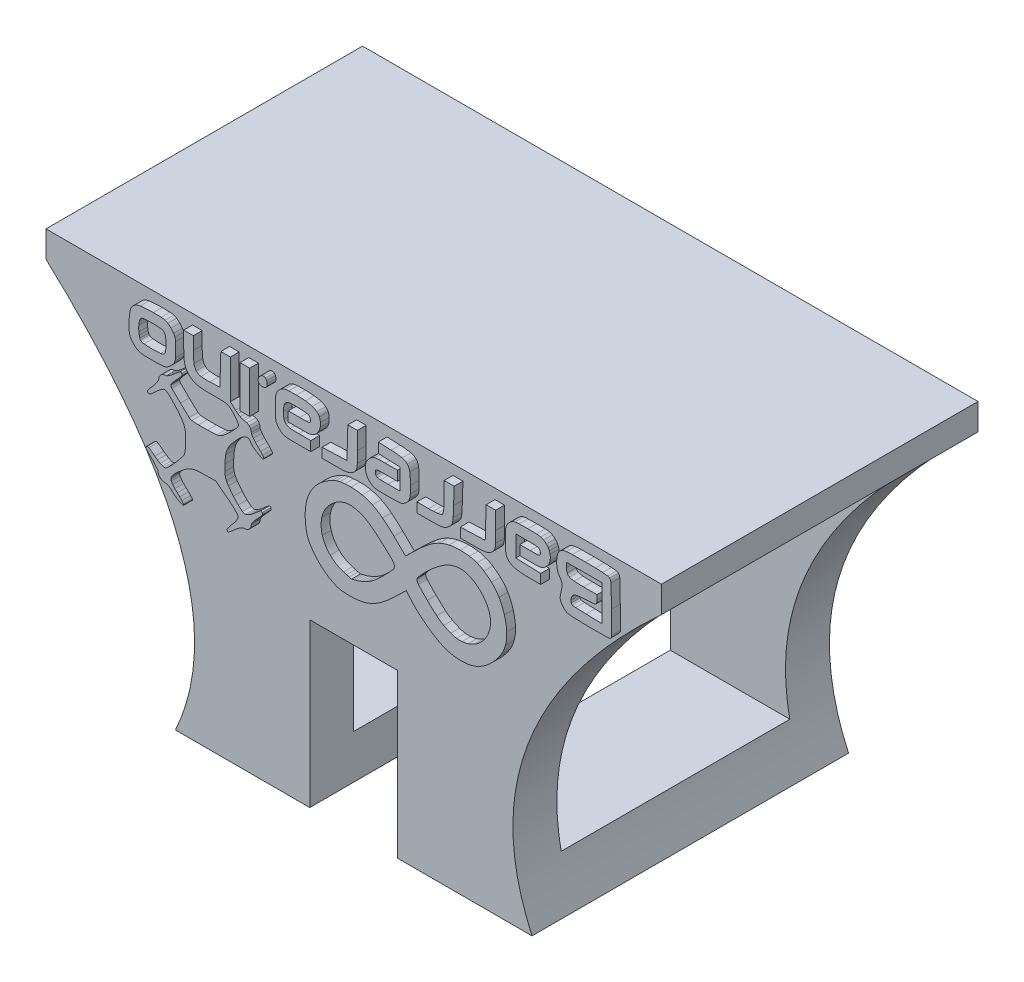
SolidWorks part; units mm, degrees
ref_plane "Alzado" through (0, 0, 0) normal (0, 0, 1) x (1, 0, 0)
ref_plane "Planta" through (0, 0, 0) normal (0, 1, 0) x (1, 0, 0)
ref_plane "Vista lateral" through (0, 0, 0) normal (1, 0, 0) x (0, 0, -1)
sketch "Croquis1" plane through (0, 0, 0) normal (0, 0, 1) x (1, 0, 0)
  line L1 (-15, 9.25) -> (15, 9.25)
  line L2 (-15, 9.25) -> (-15, -9.25)
  line L3 (-15, -9.25) -> (15, -9.25)
  line L4 (15, 9.25) -> (15, -9.25)
  line L5 (-15, 9.25) -> (15, -9.25) construction
  line L6 (-15, -9.25) -> (15, 9.25) construction
  point P0 (0, 0)
  dimension "D1" = 30
  dimension "D2" = 18.5
extrude "Saliente-Extruir1" add sketch "Croquis1" along normal blind 13
shell "Vaciado2" thickness 2.5 removed face at (0, 9.25, 6.5) outward yes
sketch "Croquis2" plane through (0, 0, -2.5) normal (0, 0, -1) x (-1, 0, 0)
  line L0 (2.5, -11.75) -> (10.1401, -11.75)
  line L1 (17.5, 9.25) -> (17.5, -11.75) construction
  line L2 (17.5, 9.25) -> (17.5, 7.75)
  line L4 (2.5, -11.75) -> (2.5, -2.5)
  line L5 (2.5, -2.5) -> (-2.5, -2.5)
  line L6 (0, -2.5) -> (0, -0.2637) construction
  line L7 (-2.5, -11.75) -> (-2.5, -2.5)
  line L8 (-17.5, 9.25) -> (-17.5, 7.75)
  line L9 (-2.5, -11.75) -> (-10.1401, -11.75)
  line L10 (17.5, 9.25) -> (-17.5, 9.25)
  line L11 (17.5, -11.75) -> (-17.5, -11.75) construction
  line L12 (17.5, 7.75) -> (17.5, -11.75)
  line L13 (17.5, -11.75) -> (10.1401, -11.75)
  line L14 (-17.5, 7.75) -> (-17.5, -11.75)
  line L15 (-17.5, -11.75) -> (-10.1401, -11.75)
  line L16 (-17.5, -11.75) -> (-17.5, 9.25) construction
  spline S0 degree 2 poles (17.5, 7.75) (6.0206, -2.776) (10.1401, -11.75) knots 0 0 0 0.858942 0.858942 0.858942
  spline S1 degree 2 poles (-17.5, 7.75) (-6.0206, -2.776) (-10.1401, -11.75) knots 0 0 0 0.858942 0.858942 0.858942
  line M13 (-17.5, -11.75) -> (17.5, -11.75)
  line M14 (17.5, -11.75) -> (17.5, 9.25)
  dimension "D1" = 1.5
  dimension "D2" = 2.5
extrude "Cortar-Extruir1" cut sketch "Croquis2" against normal blind 33 contours S0 M14 M13 | S1 L14 M13 | L7 L4 L5 M13 region at (0, -7.125, -2.5) region at (-13.9189, -3.9974, -2.5) region at (13.9189, -3.9974, -2.5)
sketch "Croquis3" plane through (0, 9.25, 0) normal (0, 1, 0) x (1, 0, 0)
  line L0 (-17.5, 2.5) -> (-17.5, -15.5)
  line L1 (-17.5, -15.5) -> (17.5, -15.5)
  line L2 (17.5, -15.5) -> (17.5, 2.5)
  line L3 (17.5, 2.5) -> (-17.5, 2.5)
extrude "Saliente-Extruir2" add sketch "Croquis3" against normal blind 1.5
sketch "Croquis4" plane through (-17.5, 0, 0) normal (-1, 0, 0) x (0, 0, 1)
  line L0 (13, -9.25) -> (13, 7.75)
  line L1 (15.5, 7.75) -> (-2.5, 7.75) construction
  line L2 (13, 7.75) -> (0, 7.75)
  line L3 (0, 7.75) -> (0, -9.25)
  line L4 (0, -9.25) -> (13, -9.25)
extrude "Cortar-Extruir2" cut sketch "Croquis4" against normal blind 36.5
sketch "Croquis5" plane through (0, 0, 15.5) normal (0, 0, 1) x (1, 0, 0)
  line L0 (-6.7264, 1.6869) -> (-7.3476, 2.1605)
  line L1 (-7.3476, 2.1605) -> (-8.0126, 2.1501)
  line L2 (-9.1685, 7.909) -> (-9.1685, 8.6803)
  line L3 (-9.1685, 8.6803) -> (-8.8942, 8.6803)
  line L4 (-8.8942, 8.6803) -> (-8.6199, 8.6803)
  line L5 (-8.6199, 8.6803) -> (-8.6199, 7.9488)
  line L6 (-7.6784, 6.8701) -> (-7.1111, 6.8972)
  line L7 (-7.1111, 6.8972) -> (-7.0849, 7.7888)
  line L8 (-7.0849, 7.7888) -> (-7.0588, 8.6803)
  line L9 (-7.0588, 8.6803) -> (-6.7878, 8.6803)
  line L10 (-6.7878, 8.6803) -> (-6.5168, 8.6803)
  line L11 (-6.5168, 8.6803) -> (-6.5168, 7.5817)
  line L12 (-6.5168, 7.5817) -> (-6.5168, 6.4832)
  line L13 (-6.5168, 6.4832) -> (-6.2196, 6.2128)
  line L14 (3.8426, 1.768) -> (3.4836, 2.1759)
  line L15 (3.4836, 2.1759) -> (2.8013, 1.5191)
  line L16 (2.7863, 4.5105) -> (3.4488, 3.8611)
  line L17 (3.4488, 3.8611) -> (4.1178, 4.5105)
  line L18 (10.5867, 7.1258) -> (9.9424, 7.1258)
  line L19 (9.9424, 7.1258) -> (9.9424, 7.4002)
  line L20 (9.9424, 7.4002) -> (9.9424, 7.6745)
  line L21 (9.9424, 7.6745) -> (10.5432, 7.6745)
  line L22 (10.3996, 8.086) -> (9.7138, 8.086)
  line L23 (9.7138, 8.086) -> (9.7138, 7.4916)
  line L24 (9.7138, 7.4916) -> (9.7138, 6.8972)
  line L25 (9.7138, 6.8972) -> (10.4225, 6.8705)
  line L26 (10.4225, 6.8705) -> (11.1312, 6.8438)
  line L27 (11.1312, 6.8438) -> (11.1312, 6.5733)
  line L28 (11.1312, 6.5733) -> (11.1312, 6.3029)
  line L29 (11.1312, 6.3029) -> (10.4408, 6.3029)
  line L30 (6.5592, 6.5733) -> (6.5592, 6.8438)
  line L31 (6.5592, 6.8438) -> (7.2678, 6.8705)
  line L32 (7.2678, 6.8705) -> (7.9765, 6.8972)
  line L33 (7.9765, 6.8972) -> (8.0027, 7.7888)
  line L34 (8.0027, 7.7888) -> (8.0288, 8.6803)
  line L35 (8.0288, 8.6803) -> (8.2998, 8.6803)
  line L36 (8.2998, 8.6803) -> (8.5708, 8.6803)
  line L37 (8.5708, 8.6803) -> (8.5708, 7.6811)
  line L38 (7.3241, 6.3029) -> (6.5592, 6.3029)
  line L39 (6.5592, 6.3029) -> (6.5592, 6.5733)
  line L40 (4.0903, 6.5772) -> (4.0903, 6.8515)
  line L41 (4.0903, 6.8515) -> (4.7578, 6.8515)
  line L42 (5.6448, 7.8756) -> (5.6448, 8.6803)
  line L43 (5.6448, 8.6803) -> (5.9274, 8.6803)
  line L44 (5.9274, 8.6803) -> (6.2101, 8.6803)
  line L45 (6.2101, 8.6803) -> (6.1789, 7.7121)
  line L46 (4.8624, 6.3029) -> (4.0903, 6.3029)
  line L47 (4.0903, 6.3029) -> (4.0903, 6.5772)
  line L48 (2.3031, 7.8574) -> (2.993, 7.8574)
  line L49 (2.993, 7.8574) -> (2.993, 7.583)
  line L50 (2.993, 7.583) -> (2.993, 7.3087)
  line L51 (2.993, 7.3087) -> (2.3466, 7.3087)
  line L52 (2.4444, 6.8972) -> (3.1302, 6.8972)
  line L53 (3.1302, 6.8972) -> (3.1302, 7.4916)
  line L54 (3.1302, 7.4916) -> (3.1302, 8.086)
  line L55 (3.1302, 8.086) -> (2.5129, 8.113)
  line L56 (2.5129, 8.113) -> (1.8957, 8.14)
  line L57 (1.8957, 8.14) -> (1.8957, 8.4199)
  line L58 (1.8957, 8.4199) -> (1.8957, 8.6997)
  line L59 (1.8957, 8.6997) -> (2.6362, 8.6661)
  line L60 (-1.3047, 6.5733) -> (-1.3047, 6.8438)
  line L61 (-1.3047, 6.8438) -> (-0.596, 6.8705)
  line L62 (-0.596, 6.8705) -> (0.1126, 6.8972)
  line L63 (0.1126, 6.8972) -> (0.1388, 7.7888)
  line L64 (0.1388, 7.7888) -> (0.165, 8.6803)
  line L65 (0.165, 8.6803) -> (0.436, 8.6803)
  line L66 (0.436, 8.6803) -> (0.707, 8.6803)
  line L67 (0.707, 8.6803) -> (0.707, 7.6811)
  line L68 (-0.5398, 6.3029) -> (-1.3047, 6.3029)
  line L69 (-1.3047, 6.3029) -> (-1.3047, 6.5733)
  line L70 (-2.535, 7.1258) -> (-3.2249, 7.1258)
  line L71 (-3.2249, 7.1258) -> (-3.2249, 7.4002)
  line L72 (-3.2249, 7.4002) -> (-3.2249, 7.6745)
  line L73 (-3.2249, 7.6745) -> (-2.5785, 7.6745)
  line L74 (-2.6273, 6.8515) -> (-1.9448, 6.8515)
  line L75 (-1.9448, 6.8515) -> (-1.9448, 6.5772)
  line L76 (-1.9448, 6.5772) -> (-1.9448, 6.3029)
  line L77 (-1.9448, 6.3029) -> (-2.7261, 6.3029)
  line L78 (-5.9681, 7.4916) -> (-5.9681, 8.6803)
  line L79 (-5.9681, 8.6803) -> (-5.6938, 8.6803)
  line L80 (-5.6938, 8.6803) -> (-5.4195, 8.6803)
  line L81 (-5.4195, 8.6803) -> (-5.4195, 7.4916)
  line L82 (-5.4195, 7.4916) -> (-5.4195, 6.3029)
  line L83 (-5.4195, 6.3029) -> (-5.6938, 6.3029)
  line L84 (-5.6938, 6.3029) -> (-5.9681, 6.3029)
  line L85 (-5.9681, 6.3029) -> (-5.9681, 7.4916)
  line L86 (0.2431, 1.2245) -> (0.3739, 1.189)
  line L87 (14.6059, 7.1225) -> (14.6059, 8.1317)
  line L88 (14.6059, 8.1317) -> (13.6, 8.1317)
  line L89 (13.6, 8.1317) -> (12.5942, 8.1317)
  line L90 (12.5942, 8.1317) -> (12.5942, 7.8756)
  line L91 (13.5726, 7.4002) -> (14.3316, 7.4002)
  line L92 (14.3316, 7.4002) -> (14.3316, 7.1362)
  line L93 (13.7143, 6.1395) -> (14.6059, 6.1134)
  line L94 (14.6059, 6.1134) -> (14.6059, 7.1225)
  arc A0 (-6.6839, 0.1379) -> (-6.6996, 0.0847) centre (-6.6016, 0.0847) ccw
  arc A1 (-6.6034, 0.2555) -> (-6.6839, 0.1379) centre (-4.3185, -1.3938) ccw
  arc A2 (-6.4976, 0.3928) -> (-6.6034, 0.2555) centre (-4.3742, -1.3536) ccw
  arc A3 (-6.3722, 0.5383) -> (-6.4976, 0.3928) centre (-3.3013, -2.2361) ccw
  arc A4 (-6.3722, 0.5383) -> (-6.2491, 0.6885) centre (-7.8715, 1.8929) ccw
  arc A5 (-6.2491, 0.6885) -> (-6.1498, 0.8402) centre (-7.4802, 1.6024) ccw
  arc A6 (-6.1498, 0.8402) -> (-6.0837, 0.9739) centre (-7.2143, 1.45) ccw
  arc A7 (-6.0837, 0.9739) -> (-6.075, 1.057) centre (-6.2161, 1.0297) ccw
  arc A8 (-6.075, 1.057) -> (-6.1181, 1.1421) centre (-6.2459, 1.0239) ccw
  arc A9 (-6.1181, 1.1421) -> (-6.2788, 1.3065) centre (-9.1303, -1.6424) ccw
  arc A10 (-6.2788, 1.3065) -> (-6.4863, 1.4941) centre (-9.1839, -1.6979) ccw
  arc A11 (-6.4863, 1.4941) -> (-6.7264, 1.6869) centre (-10.4438, -3.1887) ccw
  arc A12 (-8.0126, 2.1501) -> (-8.4856, 2.1181) centre (-7.9414, -2.4118) ccw
  arc A13 (-8.4856, 2.1181) -> (-8.8052, 2.0314) centre (-8.3493, 0.9838) ccw
  arc A14 (-8.8052, 2.0314) -> (-9.1088, 1.8499) centre (-8.2532, 0.7631) ccw
  arc A15 (-9.1088, 1.8499) -> (-9.5418, 1.4846) centre (-3.9405, -4.7153) ccw
  arc A16 (-9.5418, 1.4846) -> (-9.6789, 1.348) centre (-8.2072, 0.0074) ccw
  arc A17 (-9.6789, 1.348) -> (-9.7948, 1.2054) centre (-8.4807, 0.2565) ccw
  arc A18 (-9.7948, 1.2054) -> (-9.8774, 1.0757) centre (-8.7272, 0.4345) ccw
  arc A19 (-9.8774, 1.0757) -> (-9.9, 0.9885) centre (-9.7209, 0.9885) ccw
  arc A20 (-9.9, 0.9885) -> (-9.877, 0.9009) centre (-9.722, 0.9885) ccw
  arc A21 (-9.877, 0.9009) -> (-9.7926, 0.7696) centre (-8.6924, 1.5697) ccw
  arc A22 (-9.7926, 0.7696) -> (-9.6743, 0.6247) centre (-8.4411, 1.7525) ccw
  arc A23 (-9.6743, 0.6247) -> (-9.5343, 0.4856) centre (-8.1452, 2.0231) ccw
  arc A24 (-9.3942, 0.3529) -> (-9.5343, 0.4856) centre (-12.3125, -2.5897) ccw
  arc A25 (-9.276, 0.2278) -> (-9.3942, 0.3529) centre (-11.2475, -1.5158) ccw
  arc A26 (-9.1853, 0.1199) -> (-9.276, 0.2278) centre (-11.3717, -1.6256) ccw
  arc A27 (-9.1685, 0.072) -> (-9.1853, 0.1199) centre (-9.2453, 0.072) ccw
  arc A28 (-9.224, 0.0333) -> (-9.1685, 0.072) centre (-9.2098, 0.072) ccw
  arc A29 (-9.4288, 0.1263) -> (-9.224, 0.0333) centre (-8.6911, 1.479) ccw
  arc A30 (-9.6633, 0.276) -> (-9.4288, 0.1263) centre (-8.4622, 1.8987) ccw
  arc A31 (-9.8458, 0.4414) -> (-9.6633, 0.276) centre (-8.9223, 1.2772) ccw
  arc A32 (-9.8458, 0.4414) -> (-9.9269, 0.5149) centre (-10.2599, 0.0667) ccw
  arc A33 (-9.9269, 0.5149) -> (-10.0263, 0.5771) centre (-10.3649, -0.0747) ccw
  arc A34 (-10.0263, 0.5771) -> (-10.1282, 0.6197) centre (-10.3337, -0.0146) ccw
  arc A35 (-10.1282, 0.6197) -> (-10.216, 0.6336) centre (-10.216, 0.3489) ccw
  arc A36 (-10.3737, 0.6604) -> (-10.216, 0.6336) centre (-10.216, 1.1106) ccw
  arc A37 (-10.5087, 0.7378) -> (-10.3737, 0.6604) centre (-10.2324, 1.0636) ccw
  arc A38 (-10.5994, 0.8524) -> (-10.5087, 0.7378) centre (-10.2682, 1.0214) ccw
  arc A39 (-10.6316, 0.986) -> (-10.5994, 0.8524) centre (-10.3376, 0.986) ccw
  arc A40 (-10.6316, 0.986) -> (-10.6532, 1.0581) centre (-10.7625, 0.986) ccw
  arc A41 (-10.6532, 1.0581) -> (-10.7457, 1.1867) centre (-12.291, -0.022) ccw
  arc A42 (-10.7457, 1.1867) -> (-10.8714, 1.3337) centre (-12.4962, -0.1825) ccw
  arc A43 (-10.8714, 1.3337) -> (-11.0202, 1.4828) centre (-13.1565, -0.7988) ccw
  arc A44 (-11.3012, 1.7729) -> (-11.0202, 1.4828) centre (-8.1957, 4.4992) ccw
  arc A45 (-11.2909, 1.8907) -> (-11.3012, 1.7729) centre (-11.2397, 1.8269) ccw
  arc A46 (-11.1513, 1.897) -> (-11.2909, 1.8907) centre (-11.2168, 1.7986) ccw
  arc A47 (-10.813, 1.6493) -> (-11.1513, 1.897) centre (-13.7376, -1.9899) ccw
  arc A48 (-10.813, 1.6493) -> (-10.6646, 1.5405) centre (-9.5138, 3.266) ccw
  arc A49 (-10.6646, 1.5405) -> (-10.5112, 1.4486) centre (-9.6371, 3.0811) ccw
  arc A50 (-10.5112, 1.4486) -> (-10.3733, 1.3833) centre (-9.778, 2.818) ccw
  arc A51 (-10.3733, 1.3833) -> (-10.2823, 1.3651) centre (-10.2823, 1.6028) ccw
  arc A52 (-10.2823, 1.3651) -> (-10.1369, 1.4187) centre (-10.2823, 1.589) ccw
  arc A53 (-10.1369, 1.4187) -> (-9.8831, 1.655) centre (-12.7471, 4.4772) ccw
  arc A54 (-9.8831, 1.655) -> (-9.5662, 2.004) centre (-13.9973, 5.7092) ccw
  arc A55 (-9.5662, 2.004) -> (-9.1803, 2.4834) centre (-22.2046, 12.5721) ccw
  arc A56 (-9.1803, 2.4834) -> (-9.1289, 2.5874) centre (-9.411, 2.6621) ccw
  arc A57 (-9.1289, 2.5874) -> (-9.0907, 2.7703) centre (-10.837, 3.0392) ccw
  arc A58 (-9.0907, 2.7703) -> (-9.0659, 3.0039) centre (-11.5655, 3.1514) ccw
  arc A59 (-9.0659, 3.0039) -> (-9.0578, 3.2787) centre (-13.7232, 3.2787) ccw
  arc A60 (-9.0578, 3.2787) -> (-9.0672, 3.6176) centre (-15.1794, 3.2787) ccw
  arc A61 (-9.0672, 3.6176) -> (-9.0989, 3.8493) centre (-10.5155, 3.5373) ccw
  arc A62 (-9.0989, 3.8493) -> (-9.161, 4.0347) centre (-9.9991, 3.651) ccw
  arc A63 (-9.161, 4.0347) -> (-9.2647, 4.2178) centre (-10.2798, 3.5225) ccw
  arc A64 (-9.2647, 4.2178) -> (-9.5264, 4.5628) centre (-12.9564, 1.6889) ccw
  arc A65 (-9.5264, 4.5628) -> (-9.8258, 4.8889) centre (-13.2728, 1.4237) ccw
  arc A66 (-9.8258, 4.8889) -> (-10.1083, 5.1502) centre (-13.5572, 1.1378) ccw
  arc A67 (-10.1083, 5.1502) -> (-10.2576, 5.2056) centre (-10.2576, 4.9765) ccw
  arc A68 (-10.2576, 5.2056) -> (-10.331, 5.1862) centre (-10.2576, 5.0573) ccw
  arc A69 (-10.331, 5.1862) -> (-10.4542, 5.1085) centre (-9.5215, 3.7649) ccw
  arc A70 (-10.4542, 5.1085) -> (-10.594, 5.0017) centre (-9.3616, 3.5346) ccw
  arc A71 (-10.594, 5.0017) -> (-10.7336, 4.8752) centre (-8.9737, 3.0728) ccw
  arc A72 (-11.0497, 4.5919) -> (-10.7336, 4.8752) centre (-14.1962, 8.4211) ccw
  arc A73 (-11.1886, 4.5835) -> (-11.0497, 4.5919) centre (-11.1249, 4.6834) ccw
  arc A74 (-11.2094, 4.6969) -> (-11.1886, 4.5835) centre (-11.1463, 4.6499) ccw
  arc A75 (-10.9498, 5.0127) -> (-11.2094, 4.6969) centre (-7.6966, 2.0737) ccw
  arc A76 (-10.9498, 5.0127) -> (-10.8135, 5.1759) centre (-12.9674, 6.8355) ccw
  arc A77 (-10.8135, 5.1759) -> (-10.6963, 5.3428) centre (-12.6411, 6.5841) ccw
  arc A78 (-10.6963, 5.3428) -> (-10.6101, 5.492) centre (-12.3463, 6.3959) ccw
  arc A79 (-10.6101, 5.492) -> (-10.583, 5.5874) centre (-10.8278, 5.6054) ccw
  arc A80 (-10.5453, 5.7213) -> (-10.583, 5.5874) centre (-10.2353, 5.5618) ccw
  arc A81 (-10.4576, 5.8335) -> (-10.5453, 5.7213) centre (-10.2064, 5.5469) ccw
  arc A82 (-10.3319, 5.9085) -> (-10.4576, 5.8335) centre (-10.1905, 5.5287) ccw
  arc A83 (-10.1854, 5.9357) -> (-10.3319, 5.9085) centre (-10.1806, 5.5022) ccw
  arc A84 (-10.1854, 5.9357) -> (-10.1157, 5.9548) centre (-10.187, 6.0783) ccw
  arc A85 (-10.1157, 5.9548) -> (-9.9872, 6.0353) centre (-11.1796, 7.7956) ccw
  arc A86 (-9.9872, 6.0353) -> (-9.8393, 6.1442) centre (-11.311, 7.9896) ccw
  arc A87 (-9.8393, 6.1442) -> (-9.6877, 6.2728) centre (-11.8554, 8.6722) ccw
  arc A88 (-9.3847, 6.5197) -> (-9.6877, 6.2728) centre (-7.1275, 3.439) ccw
  arc A89 (-9.2775, 6.494) -> (-9.3847, 6.5197) centre (-9.342, 6.4614) ccw
  arc A90 (-9.2932, 6.3488) -> (-9.2775, 6.494) centre (-9.3972, 6.4335) ccw
  arc A91 (-9.5696, 6.0392) -> (-9.2932, 6.3488) centre (-12.886, 9.2776) ccw
  arc A92 (-9.5696, 6.0392) -> (-9.6961, 5.9023) centre (-7.1457, 3.6724) ccw
  arc A93 (-9.6961, 5.9023) -> (-9.803, 5.7707) centre (-7.9527, 4.378) ccw
  arc A94 (-9.803, 5.7707) -> (-9.883, 5.657) centre (-8.0409, 4.4443) ccw
  arc A95 (-9.883, 5.657) -> (-9.9, 5.6002) centre (-9.7967, 5.6002) ccw
  arc A96 (-9.9, 5.6002) -> (-9.8473, 5.4743) centre (-9.7232, 5.6002) ccw
  arc A97 (-9.8473, 5.4743) -> (-9.3542, 4.9963) centre (18.4234, 34.1502) ccw
  arc A98 (-9.3542, 4.9963) -> (-8.8588, 4.5338) centre (13.5798, 29.0666) ccw
  arc A99 (-8.8588, 4.5338) -> (-8.7061, 4.4626) centre (-8.6692, 4.7411) ccw
  arc A100 (-8.7061, 4.4626) -> (-8.3304, 4.4344) centre (-8.2693, 7.7577) ccw
  arc A101 (-8.3304, 4.4344) -> (-7.8084, 4.4363) centre (-8.1121, 16.3088) ccw
  arc A102 (-7.8084, 4.4363) -> (-7.2948, 4.4568) centre (-8.2646, 22.2703) ccw
  arc A103 (-7.2948, 4.4568) -> (-7.1168, 4.5033) centre (-7.3198, 4.9166) ccw
  arc A104 (-7.1168, 4.5033) -> (-6.8501, 4.6802) centre (-7.6648, 5.619) ccw
  arc A105 (-6.8501, 4.6802) -> (-6.4757, 5.0284) centre (-11.7243, 10.2963) ccw
  arc A106 (-6.4757, 5.0284) -> (-6.1209, 5.3986) centre (-14.2929, 12.8743) ccw
  arc A107 (-6.1209, 5.3986) -> (-6.0596, 5.5567) centre (-6.2936, 5.5567) ccw
  arc A108 (-6.0596, 5.5567) -> (-6.0777, 5.6308) centre (-6.2204, 5.5567) ccw
  arc A109 (-6.0777, 5.6308) -> (-6.1454, 5.7463) centre (-7.2404, 5.0267) ccw
  arc A110 (-6.1454, 5.7463) -> (-6.2399, 5.8754) centre (-7.464, 4.8797) ccw
  arc A111 (-6.2399, 5.8754) -> (-6.3518, 6.0013) centre (-7.744, 4.652) ccw
  arc A112 (-6.3518, 6.0013) -> (-6.5536, 6.1831) centre (-7.7907, 4.6067) ccw
  arc A113 (-6.5536, 6.1831) -> (-6.7181, 6.2645) centre (-6.8306, 5.8302) ccw
  arc A114 (-6.7181, 6.2645) -> (-6.9496, 6.2967) centre (-6.9727, 5.2814) ccw
  arc A115 (-6.9496, 6.2967) -> (-7.5177, 6.3032) centre (-7.5276, -19.1492) ccw
  arc A116 (-7.9847, 6.3112) -> (-7.5177, 6.3032) centre (-7.5122, 20.3752) ccw
  arc A117 (-8.2796, 6.339) -> (-7.9847, 6.3112) centre (-7.9025, 8.7573) ccw
  arc A118 (-8.4964, 6.3937) -> (-8.2796, 6.339) centre (-8.0935, 7.5323) ccw
  arc A119 (-8.6907, 6.4861) -> (-8.4964, 6.3937) centre (-8.1498, 7.3734) ccw
  arc A120 (-8.9332, 6.6896) -> (-8.6907, 6.4861) centre (-8.1417, 7.3867) ccw
  arc A121 (-9.0768, 6.9387) -> (-8.9332, 6.6896) centre (-8.3876, 7.1701) ccw
  arc A122 (-9.1487, 7.3034) -> (-9.0768, 6.9387) centre (-7.7105, 7.3975) ccw
  arc A123 (-9.1685, 7.909) -> (-9.1487, 7.3034) centre (0.1055, 7.909) ccw
  arc A124 (-8.6199, 7.9488) -> (-8.586, 7.3308) centre (-2.972, 7.9488) ccw
  arc A125 (-8.586, 7.3308) -> (-8.4542, 7.0307) centre (-8.0419, 7.3907) ccw
  arc A126 (-8.4542, 7.0307) -> (-8.1894, 6.8898) centre (-8.137, 7.3076) ccw
  arc A127 (-8.1894, 6.8898) -> (-7.6784, 6.8701) centre (-7.8201, 9.8354) ccw
  arc A128 (-6.2196, 6.2128) -> (-6.092, 6.1092) centre (-5.2258, 7.3052) ccw
  arc A129 (-6.092, 6.1092) -> (-5.9546, 6.0211) centre (-5.25, 7.2718) ccw
  arc A130 (-5.9546, 6.0211) -> (-5.8271, 5.9589) centre (-5.3669, 7.0644) ccw
  arc A131 (-5.8271, 5.9589) -> (-5.7349, 5.9398) centre (-5.7314, 6.1887) ccw
  arc A132 (-5.5763, 5.9095) -> (-5.7349, 5.9398) centre (-5.7416, 5.4742) ccw
  arc A133 (-5.4449, 5.8272) -> (-5.5763, 5.9095) centre (-5.7173, 5.5381) ccw
  arc A134 (-5.3585, 5.7039) -> (-5.4449, 5.8272) centre (-5.6996, 5.5569) ccw
  arc A135 (-5.328, 5.5564) -> (-5.3585, 5.7039) centre (-5.7008, 5.5564) ccw
  arc A136 (-5.328, 5.5564) -> (-5.3047, 5.472) centre (-5.1637, 5.5564) ccw
  arc A137 (-5.3047, 5.472) -> (-5.214, 5.3361) centre (-3.8903, 6.3178) ccw
  arc A138 (-5.214, 5.3361) -> (-5.0885, 5.1835) centre (-3.6294, 6.5113) ccw
  arc A139 (-5.0885, 5.1835) -> (-4.94, 5.0331) centre (-3.1775, 6.9225) ccw
  arc A140 (-4.7957, 4.8898) -> (-4.94, 5.0331) centre (-7.1299, 2.6854) ccw
  arc A141 (-4.6845, 4.7589) -> (-4.7957, 4.8898) centre (-5.9924, 3.7597) ccw
  arc A142 (-4.6101, 4.6511) -> (-4.6845, 4.7589) centre (-5.7577, 3.9389) ccw
  arc A143 (-4.6151, 4.6079) -> (-4.6101, 4.6511) centre (-4.6399, 4.6326) ccw
  arc A144 (-4.721, 4.5905) -> (-4.6151, 4.6079) centre (-4.6801, 4.6729) ccw
  arc A145 (-4.9942, 4.7425) -> (-4.721, 4.5905) centre (-3.2414, 7.5729) ccw
  arc A146 (-5.2549, 4.9251) -> (-4.9942, 4.7425) centre (-3.5141, 7.1325) ccw
  arc A147 (-5.3618, 5.0703) -> (-5.2549, 4.9251) centre (-5.0444, 5.1921) ccw
  arc A148 (-5.3618, 5.0703) -> (-5.4656, 5.1779) centre (-5.5408, 5.0016) ccw
  arc A149 (-5.4656, 5.1779) -> (-5.624, 5.1874) centre (-5.5579, 4.9613) ccw
  arc A150 (-5.624, 5.1874) -> (-5.833, 5.0803) centre (-5.4488, 4.5876) ccw
  arc A151 (-5.833, 5.0803) -> (-6.0724, 4.8627) centre (-4.5139, 3.3889) ccw
  arc A152 (-6.0724, 4.8627) -> (-6.4656, 4.4152) centre (-0.1496, -0.738) ccw
  arc A153 (-6.4656, 4.4152) -> (-6.6733, 4.0854) centre (-5.228, 3.4055) ccw
  arc A154 (-6.6733, 4.0854) -> (-6.7788, 3.7419) centre (-5.5212, 3.5434) ccw
  arc A155 (-6.7788, 3.7419) -> (-6.8246, 3.2637) centre (-2.8908, 3.1283) ccw
  arc A156 (-6.8246, 3.2637) -> (-6.829, 2.8855) centre (1.4053, 2.9803) ccw
  arc A157 (-6.829, 2.8855) -> (-6.8046, 2.6591) centre (-5.636, 2.8992) ccw
  arc A158 (-6.8046, 2.6591) -> (-6.7421, 2.4793) centre (-6.0966, 2.8046) ccw
  arc A159 (-6.7421, 2.4793) -> (-6.6223, 2.2795) centre (-5.3189, 3.1966) ccw
  arc A160 (-6.6223, 2.2795) -> (-6.3422, 1.9121) centre (-1.6959, 5.7454) ccw
  arc A161 (-6.3422, 1.9121) -> (-6.0706, 1.6202) centre (-3.7566, 4.0453) ccw
  arc A162 (-6.0706, 1.6202) -> (-5.8306, 1.4195) centre (-4.4204, 3.3496) ccw
  arc A163 (-5.8306, 1.4195) -> (-5.6641, 1.3651) centre (-5.6641, 1.6474) ccw
  arc A164 (-5.6641, 1.3651) -> (-5.5724, 1.3861) centre (-5.6641, 1.5759) ccw
  arc A165 (-5.5724, 1.3861) -> (-5.4301, 1.4637) centre (-6.2789, 2.8501) ccw
  arc A166 (-5.4301, 1.4637) -> (-5.271, 1.5723) centre (-6.4477, 3.1257) ccw
  arc A167 (-5.271, 1.5723) -> (-5.1157, 1.7008) centre (-6.6795, 3.4317) ccw
  arc A168 (-4.8127, 1.9477) -> (-5.1157, 1.7008) centre (-2.5555, -1.133) ccw
  arc A169 (-4.7055, 1.922) -> (-4.8127, 1.9477) centre (-4.77, 1.8894) ccw
  arc A170 (-4.7212, 1.7768) -> (-4.7055, 1.922) centre (-4.8252, 1.8615) ccw
  arc A171 (-4.9976, 1.4672) -> (-4.7212, 1.7768) centre (-8.314, 4.7056) ccw
  arc A172 (-4.9976, 1.4672) -> (-5.1241, 1.3275) centre (-3.1985, -0.2895) ccw
  arc A173 (-5.1241, 1.3275) -> (-5.231, 1.1877) centre (-3.6585, 0.0967) ccw
  arc A174 (-5.231, 1.1877) -> (-5.3086, 1.0644) centre (-3.8891, 0.2568) ccw
  arc A175 (-5.3086, 1.0644) -> (-5.328, 0.9909) centre (-5.1794, 0.9909) ccw
  arc A176 (-5.359, 0.8573) -> (-5.328, 0.9909) centre (-5.6318, 0.9909) ccw
  arc A177 (-5.4468, 0.7408) -> (-5.359, 0.8573) centre (-5.7049, 1.0267) ccw
  arc A178 (-5.5758, 0.6613) -> (-5.4468, 0.7408) centre (-5.7273, 1.0515) ccw
  arc A179 (-5.7239, 0.6336) -> (-5.5758, 0.6613) centre (-5.7239, 1.0427) ccw
  arc A180 (-5.7239, 0.6336) -> (-5.8145, 0.6134) centre (-5.7239, 0.4205) ccw
  arc A181 (-5.8145, 0.6134) -> (-5.9525, 0.5396) centre (-5.1709, -0.7563) ccw
  arc A182 (-5.9525, 0.5396) -> (-6.1059, 0.4361) centre (-5.0118, -1.02) ccw
  arc A183 (-6.1059, 0.4361) -> (-6.2545, 0.3136) centre (-4.8247, -1.269) ccw
  arc A184 (-6.5026, 0.0947) -> (-6.2545, 0.3136) centre (-15.5194, 10.5688) ccw
  arc A185 (-6.6179, 0.0171) -> (-6.5026, 0.0947) centre (-6.8879, 0.5423) ccw
  arc A186 (-6.673, 0.0244) -> (-6.6179, 0.0171) centre (-6.6402, 0.0604) ccw
  arc A187 (-6.6996, 0.0847) -> (-6.673, 0.0244) centre (-6.618, 0.0847) ccw
  arc A188 (5.3103, 0.6183) -> (5.7623, 0.4151) centre (6.5706, 2.8174) ccw
  arc A189 (4.7723, 0.9609) -> (5.3103, 0.6183) centre (8.7026, 6.5373) ccw
  arc A190 (4.2504, 1.3663) -> (4.7723, 0.9609) centre (8.8746, 6.7814) ccw
  arc A191 (3.8426, 1.768) -> (4.2504, 1.3663) centre (6.8662, 4.4295) ccw
  arc A192 (2.1385, 0.9426) -> (2.8013, 1.5191) centre (-3.2225, 7.7757) ccw
  arc A193 (1.5585, 0.5787) -> (2.1385, 0.9426) centre (0.1215, 3.5135) ccw
  arc A194 (0.9831, 0.3808) -> (1.5585, 0.5787) centre (0.477, 2.7874) ccw
  arc A195 (0.3412, 0.3145) -> (0.9831, 0.3808) centre (0.3454, 3.4135) ccw
  arc A196 (-0.0479, 0.326) -> (0.3412, 0.3145) centre (0.3503, 7.1886) ccw
  arc A197 (-0.3108, 0.3639) -> (-0.0479, 0.326) centre (0.0426, 1.886) ccw
  arc A198 (-0.547, 0.443) -> (-0.3108, 0.3639) centre (-0.0142, 1.6413) ccw
  arc A199 (-0.8404, 0.5888) -> (-0.547, 0.443) centre (1.0094, 3.9434) ccw
  arc A200 (-1.242, 0.8656) -> (-0.8404, 0.5888) centre (0.3442, 2.737) ccw
  arc A201 (-1.6262, 1.2436) -> (-1.242, 0.8656) centre (1.112, 3.6429) ccw
  arc A202 (-1.9429, 1.6651) -> (-1.6262, 1.2436) centre (1.015, 3.5579) ccw
  arc A203 (-2.1404, 2.0725) -> (-1.9429, 1.6651) centre (-0.3215, 2.7027) ccw
  arc A204 (-2.1865, 2.2484) -> (-2.1404, 2.0725) centre (-1.0263, 2.4585) ccw
  arc A205 (-2.2254, 2.5036) -> (-2.1865, 2.2484) centre (2.3482, 3.0696) ccw
  arc A206 (-2.2525, 2.7865) -> (-2.2254, 2.5036) centre (2.8867, 3.1363) ccw
  arc A207 (-2.2622, 3.0568) -> (-2.2525, 2.7865) centre (1.9671, 3.0737) ccw
  arc A208 (-2.1649, 3.8127) -> (-2.2622, 3.0568) centre (0.6309, 3.0683) ccw
  arc A209 (-1.8738, 4.4818) -> (-2.1649, 3.8127) centre (0.1919, 3.1852) ccw
  arc A210 (-1.3909, 5.0467) -> (-1.8738, 4.4818) centre (0.2793, 3.1303) ccw
  arc A211 (-0.7306, 5.4968) -> (-1.3909, 5.0467) centre (0.829, 2.4996) ccw
  arc A212 (-0.5077, 5.5938) -> (-0.7306, 5.4968) centre (0.0792, 3.9406) ccw
  arc A213 (-0.2803, 5.6555) -> (-0.5077, 5.5938) centre (0.0106, 4.1339) ccw
  arc A214 (-0.012, 5.6895) -> (-0.2803, 5.6555) centre (0.1239, 3.541) ccw
  arc A215 (0.3412, 5.7017) -> (-0.012, 5.6895) centre (0.3773, -0.464) ccw
  arc A216 (0.9875, 5.6382) -> (0.3412, 5.7017) centre (0.3596, 2.5698) ccw
  arc A217 (1.5638, 5.4423) -> (0.9875, 5.6382) centre (0.501, 3.2611) ccw
  arc A218 (2.1385, 5.0811) -> (1.5638, 5.4423) centre (0.1816, 2.6053) ccw
  arc A219 (2.7863, 4.5105) -> (2.1385, 5.0811) centre (-2.8879, -1.278) ccw
  arc A220 (4.7694, 5.0803) -> (4.1178, 4.5105) centre (9.9304, -1.4781) ccw
  arc A221 (5.344, 5.4412) -> (4.7694, 5.0803) centre (6.7536, 2.5589) ccw
  arc A222 (5.9174, 5.638) -> (5.344, 5.4412) centre (6.4192, 3.2427) ccw
  arc A223 (6.5592, 5.7044) -> (5.9174, 5.638) centre (6.5584, 2.578) ccw
  arc A224 (7.0796, 5.6677) -> (6.5592, 5.7044) centre (6.5583, 1.9848) ccw
  arc A225 (7.5072, 5.5562) -> (7.0796, 5.6677) centre (6.8086, 3.7536) ccw
  arc A226 (7.9052, 5.3482) -> (7.5072, 5.5562) centre (6.7803, 3.6805) ccw
  arc A227 (8.336, 5.0159) -> (7.9052, 5.3482) centre (5.5103, 1.7975) ccw
  arc A228 (8.7648, 4.4877) -> (8.336, 5.0159) centre (6.9969, 3.4907) ccw
  arc A229 (9.0668, 3.7719) -> (8.7648, 4.4877) centre (5.7974, 2.8143) ccw
  arc A230 (9.2, 3.0016) -> (9.0668, 3.7719) centre (5.7594, 2.8031) ccw
  arc A231 (9.1284, 2.3108) -> (9.2, 3.0016) centre (7.0366, 2.8768) ccw
  arc A232 (8.8635, 1.7024) -> (9.1284, 2.3108) centre (6.9334, 2.9047) ccw
  arc A233 (8.4064, 1.1156) -> (8.8635, 1.7024) centre (5.842, 3.5846) ccw
  arc A234 (7.8419, 0.6411) -> (8.4064, 1.1156) centre (5.8804, 3.5476) ccw
  arc A235 (7.2573, 0.3674) -> (7.8419, 0.6411) centre (6.6783, 2.3653) ccw
  arc A236 (6.9038, 0.2972) -> (7.2573, 0.3674) centre (6.6738, 2.3809) ccw
  arc A237 (6.5193, 0.2822) -> (6.9038, 0.2972) centre (6.6058, 2.997) ccw
  arc A238 (6.13, 0.3219) -> (6.5193, 0.2822) centre (6.6086, 3.0844) ccw
  arc A239 (5.7623, 0.4151) -> (6.13, 0.3219) centre (6.5535, 2.7665) ccw
  arc A240 (12.2845, 6.0194) -> (12.3822, 5.866) centre (13.3684, 6.6017) ccw
  arc A241 (12.2441, 6.1458) -> (12.2845, 6.0194) centre (12.605, 6.1916) ccw
  arc A242 (12.2466, 6.2966) -> (12.2441, 6.1458) centre (12.7692, 6.2124) ccw
  arc A243 (12.2956, 6.548) -> (12.2466, 6.2966) centre (16.121, 5.6726) ccw
  arc A244 (12.2956, 6.548) -> (12.3443, 6.7964) centre (8.3509, 7.4506) ccw
  arc A245 (12.3443, 6.7964) -> (12.3478, 6.9449) centre (11.8137, 6.8833) ccw
  arc A246 (12.3478, 6.9449) -> (12.3102, 7.0652) centre (12.0138, 6.9064) ccw
  arc A247 (12.3102, 7.0652) -> (12.2201, 7.2029) centre (11.4786, 6.6196) ccw
  arc A248 (12.0832, 7.4871) -> (12.2201, 7.2029) centre (12.7946, 7.6548) ccw
  arc A249 (12.0395, 7.8737) -> (12.0832, 7.4871) centre (13.6788, 7.8632) ccw
  arc A250 (12.0875, 8.2493) -> (12.0395, 7.8737) centre (13.6123, 7.8636) ccw
  arc A251 (12.2284, 8.4974) -> (12.0875, 8.2493) centre (12.6083, 8.1176) ccw
  arc A252 (12.3799, 8.5975) -> (12.2284, 8.4974) centre (12.549, 8.1769) ccw
  arc A253 (12.5853, 8.6508) -> (12.3799, 8.5975) centre (12.6895, 7.8272) ccw
  arc A254 (12.9299, 8.675) -> (12.5853, 8.6508) centre (12.974, 5.5799) ccw
  arc A255 (13.6732, 8.6803) -> (12.9299, 8.675) centre (13.6732, -43.4883) ccw
  arc A256 (14.2465, 8.6741) -> (13.6732, 8.6803) centre (13.6732, -17.8748) ccw
  arc A257 (14.6533, 8.6535) -> (14.2465, 8.6741) centre (14.0955, 1.6809) ccw
  arc A258 (14.9421, 8.6218) -> (14.6533, 8.6535) centre (14.2614, 3.7551) ccw
  arc A259 (15.0448, 8.5706) -> (14.9421, 8.6218) centre (14.917, 8.4428) ccw
  arc A260 (15.129, 8.3748) -> (15.0448, 8.5706) centre (14.8412, 8.367) ccw
  arc A261 (15.1563, 7.0988) -> (15.129, 8.3748) centre (-97.2204, 5.3295) ccw
  arc A262 (15.1694, 5.8202) -> (15.1563, 7.0988) centre (-100.7371, 5.274) ccw
  arc A263 (15.0911, 5.6298) -> (15.1694, 5.8202) centre (14.902, 5.8189) ccw
  arc A264 (15.0344, 5.605) -> (15.0911, 5.6298) centre (15.0309, 5.6901) ccw
  arc A265 (14.685, 5.5925) -> (15.0344, 5.605) centre (13.8624, 33.5165) ccw
  arc A266 (14.2737, 5.5866) -> (14.685, 5.5925) centre (14.2863, 19.1266) ccw
  arc A267 (13.7978, 5.5917) -> (14.2737, 5.5866) centre (14.2962, 29.7988) ccw
  arc A268 (12.9929, 5.613) -> (13.7978, 5.5917) centre (15.2164, 74.4898) ccw
  arc A269 (12.7017, 5.6457) -> (12.9929, 5.613) centre (13.0524, 7.4558) ccw
  arc A270 (12.5314, 5.7193) -> (12.7017, 5.6457) centre (12.7838, 6.0698) ccw
  arc A271 (12.3822, 5.866) -> (12.5314, 5.7193) centre (12.933, 6.2769) ccw
  arc A272 (9.2894, 6.5794) -> (9.4918, 6.4367) centre (9.9081, 7.2418) ccw
  arc A273 (9.1806, 6.7486) -> (9.2894, 6.5794) centre (9.5689, 6.8786) ccw
  arc A274 (9.1312, 7.0149) -> (9.1806, 6.7486) centre (10.1039, 7.0577) ccw
  arc A275 (9.1195, 7.5489) -> (9.1312, 7.0149) centre (21.2676, 7.549) ccw
  arc A276 (9.1271, 7.9407) -> (9.1195, 7.5489) centre (19.1604, 7.549) ccw
  arc A277 (9.1574, 8.1541) -> (9.1271, 7.9407) centre (10.1869, 7.8993) ccw
  arc A278 (9.223, 8.3061) -> (9.1574, 8.1541) centre (9.6463, 8.0331) ccw
  arc A279 (9.3439, 8.4559) -> (9.223, 8.3061) centre (9.9854, 7.8144) ccw
  arc A280 (9.5009, 8.5799) -> (9.3439, 8.4559) centre (9.9528, 7.847) ccw
  arc A281 (9.6636, 8.6451) -> (9.5009, 8.5799) centre (9.7703, 8.1429) ccw
  arc A282 (9.9049, 8.6737) -> (9.6636, 8.6451) centre (9.9403, 7.3434) ccw
  arc A283 (10.3996, 8.6803) -> (9.9049, 8.6737) centre (10.3996, -9.9113) ccw
  arc A284 (10.8944, 8.6737) -> (10.3996, 8.6803) centre (10.3997, -9.9113) ccw
  arc A285 (11.1357, 8.6451) -> (10.8944, 8.6737) centre (10.859, 7.3434) ccw
  arc A286 (11.2984, 8.5799) -> (11.1357, 8.6451) centre (11.029, 8.1429) ccw
  arc A287 (11.4554, 8.4559) -> (11.2984, 8.5799) centre (10.8465, 7.847) ccw
  arc A288 (11.556, 8.3354) -> (11.4554, 8.4559) centre (10.8369, 7.8374) ccw
  arc A289 (11.6257, 8.2064) -> (11.556, 8.3354) centre (11.0069, 7.9551) ccw
  arc A290 (11.6662, 8.0639) -> (11.6257, 8.2064) centre (10.9923, 7.9492) ccw
  arc A291 (11.6798, 7.9031) -> (11.6662, 8.0639) centre (10.7211, 7.9031) ccw
  arc A292 (11.6662, 7.7423) -> (11.6798, 7.9031) centre (10.7211, 7.9031) ccw
  arc A293 (11.6257, 7.5998) -> (11.6662, 7.7423) centre (10.9923, 7.8569) ccw
  arc A294 (11.556, 7.4708) -> (11.6257, 7.5998) centre (11.0069, 7.851) ccw
  arc A295 (11.4554, 7.3503) -> (11.556, 7.4708) centre (10.8369, 7.9687) ccw
  arc A296 (11.3077, 7.2305) -> (11.4554, 7.3503) centre (10.8065, 7.9992) ccw
  arc A297 (11.1584, 7.1646) -> (11.3077, 7.2305) centre (11.0322, 7.653) ccw
  arc A298 (10.9523, 7.1338) -> (11.1584, 7.1646) centre (10.9086, 8.1313) ccw
  arc A299 (10.5867, 7.1258) -> (10.9523, 7.1338) centre (10.5867, 15.4848) ccw
  arc A300 (10.5432, 7.6745) -> (10.9189, 7.6789) centre (10.5432, 23.4717) ccw
  arc A301 (10.9189, 7.6789) -> (11.0533, 7.7041) centre (10.9088, 8.1056) ccw
  arc A302 (11.0533, 7.7041) -> (11.1083, 7.7645) centre (11.0238, 7.7862) ccw
  arc A303 (11.1083, 7.7645) -> (11.1147, 7.8802) centre (10.82, 7.8384) ccw
  arc A304 (11.1147, 7.8802) -> (11.0711, 7.9942) centre (10.8427, 7.8416) ccw
  arc A305 (11.0711, 7.9942) -> (10.9875, 8.0553) centre (10.9458, 7.9105) ccw
  arc A306 (10.9875, 8.0553) -> (10.8198, 8.081) centre (10.804, 7.4175) ccw
  arc A307 (10.8198, 8.081) -> (10.3996, 8.086) centre (10.3997, -9.557) ccw
  arc A308 (10.1369, 6.3118) -> (10.4408, 6.3029) centre (10.4408, 11.5009) ccw
  arc A309 (9.8662, 6.3387) -> (10.1369, 6.3118) centre (10.3321, 9.6438) ccw
  arc A310 (9.643, 6.3807) -> (9.8662, 6.3387) centre (10.2124, 8.7947) ccw
  arc A311 (9.4918, 6.4367) -> (9.643, 6.3807) centre (9.7941, 7.0213) ccw
  arc A312 (8.5656, 7.0444) -> (8.5708, 7.6811) centre (-29.9471, 7.6811) ccw
  arc A313 (8.5381, 6.7918) -> (8.5656, 7.0444) centre (7.1791, 7.0673) ccw
  arc A314 (8.4693, 6.6364) -> (8.5381, 6.7918) centre (8.1511, 6.8703) ccw
  arc A315 (8.3299, 6.4924) -> (8.4693, 6.6364) centre (7.8702, 7.0768) ccw
  arc A316 (8.1698, 6.3952) -> (8.3299, 6.4924) centre (7.8503, 7.1022) ccw
  arc A317 (7.9902, 6.3386) -> (8.1698, 6.3952) centre (7.8435, 7.117) ccw
  arc A318 (7.7393, 6.3105) -> (7.9902, 6.3386) centre (7.6772, 8) ccw
  arc A319 (7.3241, 6.3029) -> (7.7393, 6.3105) centre (7.3241, 17.6015) ccw
  arc A320 (4.7578, 6.8515) -> (5.0354, 6.859) centre (4.7578, 12.0193) ccw
  arc A321 (5.0354, 6.859) -> (5.2709, 6.8819) centre (4.8884, 9.591) ccw
  arc A322 (5.2709, 6.8819) -> (5.4534, 6.9159) centre (4.9764, 8.968) ccw
  arc A323 (5.4534, 6.9159) -> (5.535, 6.9612) centre (5.415, 7.0813) ccw
  arc A324 (5.535, 6.9612) -> (5.5823, 7.0491) centre (5.4125, 7.0838) ccw
  arc A325 (5.5823, 7.0491) -> (5.6157, 7.2552) centre (3.0906, 7.5582) ccw
  arc A326 (5.6157, 7.2552) -> (5.6377, 7.5304) centre (2.1348, 7.6729) ccw
  arc A327 (5.6377, 7.5304) -> (5.6448, 7.8756) centre (-2.8466, 7.8756) ccw
  arc A328 (6.1534, 7.1042) -> (6.1789, 7.7121) centre (-25.3073, 8.7262) ccw
  arc A329 (6.1162, 6.8484) -> (6.1534, 7.1042) centre (4.7635, 7.1758) ccw
  arc A330 (6.0398, 6.6841) -> (6.1162, 6.8484) centre (5.6675, 6.957) ccw
  arc A331 (5.8911, 6.5234) -> (6.0398, 6.6841) centre (5.2645, 7.2524) ccw
  arc A332 (5.7201, 6.4043) -> (5.8911, 6.5234) centre (5.2235, 7.3002) ccw
  arc A333 (5.5481, 6.3399) -> (5.7201, 6.4043) centre (5.4171, 6.9509) ccw
  arc A334 (5.3073, 6.3103) -> (5.5481, 6.3399) centre (5.2619, 7.6751) ccw
  arc A335 (4.8624, 6.3029) -> (5.3073, 6.3103) centre (4.8624, 19.6664) ccw
  arc A336 (1.2881, 6.6478) -> (1.3887, 6.5273) centre (2.0071, 7.1458) ccw
  arc A337 (1.2183, 6.7768) -> (1.2881, 6.6478) centre (1.8371, 7.0281) ccw
  arc A338 (1.1778, 6.9193) -> (1.2183, 6.7768) centre (1.8517, 7.034) ccw
  arc A339 (1.1642, 7.0801) -> (1.1778, 6.9193) centre (2.1229, 7.0801) ccw
  arc A340 (1.1778, 7.2409) -> (1.1642, 7.0801) centre (2.1229, 7.0801) ccw
  arc A341 (1.2183, 7.3834) -> (1.1778, 7.2409) centre (1.8517, 7.1263) ccw
  arc A342 (1.2881, 7.5124) -> (1.2183, 7.3834) centre (1.8371, 7.1322) ccw
  arc A343 (1.3887, 7.6329) -> (1.2881, 7.5124) centre (2.0071, 7.0145) ccw
  arc A344 (1.5388, 7.754) -> (1.3887, 7.6329) centre (2.0286, 6.993) ccw
  arc A345 (1.6914, 7.8196) -> (1.5388, 7.754) centre (1.8114, 7.3304) ccw
  arc A346 (1.9062, 7.8498) -> (1.6914, 7.8196) centre (1.9472, 6.7774) ccw
  arc A347 (2.3031, 7.8574) -> (1.9062, 7.8498) centre (2.3031, -2.5366) ccw
  arc A348 (2.3466, 7.3087) -> (1.9388, 7.3044) centre (2.3466, -11.9477) ccw
  arc A349 (1.9388, 7.3044) -> (1.7957, 7.2796) centre (1.9491, 6.8194) ccw
  arc A350 (1.7957, 7.2796) -> (1.7374, 7.2188) centre (1.8243, 7.1938) ccw
  arc A351 (1.7374, 7.2188) -> (1.7293, 7.103) centre (2.0045, 7.1421) ccw
  arc A352 (1.7293, 7.103) -> (1.7729, 6.989) centre (2.0013, 7.1416) ccw
  arc A353 (1.7729, 6.989) -> (1.8565, 6.9279) centre (1.8982, 7.0727) ccw
  arc A354 (1.8565, 6.9279) -> (2.0242, 6.9022) centre (2.04, 7.5657) ccw
  arc A355 (2.0242, 6.9022) -> (2.4444, 6.8972) centre (2.4443, 24.5402) ccw
  arc A356 (3.255, 8.5995) -> (2.6362, 8.6661) centre (2.4076, 3.6332) ccw
  arc A357 (3.5479, 8.4398) -> (3.255, 8.5995) centre (3.1685, 8.0924) ccw
  arc A358 (3.6886, 8.1295) -> (3.5479, 8.4398) centre (3.1432, 8.0692) ccw
  arc A359 (3.7245, 7.4773) -> (3.6886, 8.1295) centre (-2.2116, 7.4773) ccw
  arc A360 (3.7172, 7.056) -> (3.7245, 7.4773) centre (-8.4561, 7.4773) ccw
  arc A361 (3.6875, 6.8344) -> (3.7172, 7.056) centre (2.5836, 7.0952) ccw
  arc A362 (3.622, 6.6793) -> (3.6875, 6.8344) centre (3.1963, 6.9504) ccw
  arc A363 (3.5001, 6.5273) -> (3.622, 6.6793) centre (2.8677, 7.1597) ccw
  arc A364 (3.3431, 6.4032) -> (3.5001, 6.5273) centre (2.8912, 7.1362) ccw
  arc A365 (3.1805, 6.3381) -> (3.3431, 6.4032) centre (3.0737, 6.8402) ccw
  arc A366 (2.9391, 6.3095) -> (3.1805, 6.3381) centre (2.9037, 7.6398) ccw
  arc A367 (2.4444, 6.3029) -> (2.9391, 6.3095) centre (2.4444, 24.8945) ccw
  arc A368 (1.9496, 6.3095) -> (2.4444, 6.3029) centre (2.4444, 24.8945) ccw
  arc A369 (1.7083, 6.3381) -> (1.9496, 6.3095) centre (1.985, 7.6398) ccw
  arc A370 (1.5456, 6.4032) -> (1.7083, 6.3381) centre (1.815, 6.8402) ccw
  arc A371 (1.3887, 6.5273) -> (1.5456, 6.4032) centre (1.9975, 7.1362) ccw
  arc A372 (0.7017, 7.0444) -> (0.707, 7.6811) centre (-37.811, 7.6811) ccw
  arc A373 (0.6743, 6.7918) -> (0.7017, 7.0444) centre (-0.6848, 7.0673) ccw
  arc A374 (0.6054, 6.6364) -> (0.6743, 6.7918) centre (0.2873, 6.8703) ccw
  arc A375 (0.4661, 6.4924) -> (0.6054, 6.6364) centre (0.0064, 7.0768) ccw
  arc A376 (0.306, 6.3952) -> (0.4661, 6.4924) centre (-0.0136, 7.1022) ccw
  arc A377 (0.1264, 6.3386) -> (0.306, 6.3952) centre (-0.0203, 7.117) ccw
  arc A378 (-0.1245, 6.3105) -> (0.1264, 6.3386) centre (-0.1867, 8) ccw
  arc A379 (-0.5398, 6.3029) -> (-0.1245, 6.3105) centre (-0.5398, 17.6015) ccw
  arc A380 (-3.8543, 6.68) -> (-3.732, 6.5273) centre (-3.1027, 7.1566) ccw
  arc A381 (-3.9197, 6.8361) -> (-3.8543, 6.68) centre (-3.4274, 6.9507) ccw
  arc A382 (-3.9493, 7.0604) -> (-3.9197, 6.8361) centre (-2.7903, 7.099) ccw
  arc A383 (-3.9564, 7.4916) -> (-3.9493, 7.0604) centre (8.9928, 7.4916) ccw
  arc A384 (-3.9493, 7.9228) -> (-3.9564, 7.4916) centre (8.9928, 7.4916) ccw
  arc A385 (-3.9197, 8.1471) -> (-3.9493, 7.9228) centre (-2.7903, 7.8842) ccw
  arc A386 (-3.8543, 8.3032) -> (-3.9197, 8.1471) centre (-3.4274, 8.0325) ccw
  arc A387 (-3.732, 8.4559) -> (-3.8543, 8.3032) centre (-3.1027, 7.8266) ccw
  arc A388 (-3.5793, 8.5782) -> (-3.732, 8.4559) centre (-3.1028, 7.8267) ccw
  arc A389 (-3.4232, 8.6436) -> (-3.5793, 8.5782) centre (-3.3086, 8.1513) ccw
  arc A390 (-3.1988, 8.6731) -> (-3.4232, 8.6436) centre (-3.1602, 7.5135) ccw
  arc A391 (-2.7673, 8.6803) -> (-3.1988, 8.6731) centre (-2.7673, -4.2893) ccw
  arc A392 (-2.2488, 8.6555) -> (-2.7673, 8.6803) centre (-2.7673, 3.2426) ccw
  arc A393 (-1.8609, 8.5766) -> (-2.2488, 8.6555) centre (-2.4283, 6.7821) ccw
  arc A394 (-1.5956, 8.4464) -> (-1.8609, 8.5766) centre (-2.1594, 7.6324) ccw
  arc A395 (-1.4529, 8.2647) -> (-1.5956, 8.4464) centre (-1.8186, 8.1244) ccw
  arc A396 (-1.3966, 8.0219) -> (-1.4529, 8.2647) centre (-2.2957, 7.9413) ccw
  arc A397 (-1.4081, 7.771) -> (-1.3966, 8.0219) centre (-2.3234, 7.9388) ccw
  arc A398 (-1.4852, 7.5388) -> (-1.4081, 7.771) centre (-2.2754, 7.93) ccw
  arc A399 (-1.6206, 7.3503) -> (-1.4852, 7.5388) centre (-2.1267, 7.8564) ccw
  arc A400 (-1.7707, 7.2292) -> (-1.6206, 7.3503) centre (-2.2605, 7.9902) ccw
  arc A401 (-1.9233, 7.1636) -> (-1.7707, 7.2292) centre (-2.0433, 7.6528) ccw
  arc A402 (-2.1381, 7.1334) -> (-1.9233, 7.1636) centre (-2.1791, 8.2058) ccw
  arc A403 (-2.535, 7.1258) -> (-2.1381, 7.1334) centre (-2.535, 17.5198) ccw
  arc A404 (-2.5785, 7.6745) -> (-2.1707, 7.6788) centre (-2.5785, 26.9308) ccw
  arc A405 (-2.1707, 7.6788) -> (-2.0276, 7.7036) centre (-2.181, 8.1638) ccw
  arc A406 (-2.0276, 7.7036) -> (-1.9693, 7.7644) centre (-2.0562, 7.7894) ccw
  arc A407 (-1.9693, 7.7644) -> (-1.9613, 7.8802) centre (-2.2365, 7.8411) ccw
  arc A408 (-1.9613, 7.8802) -> (-2.004, 7.9933) centre (-2.2357, 7.8412) ccw
  arc A409 (-2.004, 7.9933) -> (-2.0865, 8.0578) centre (-2.1404, 7.9038) ccw
  arc A410 (-2.0865, 8.0578) -> (-2.2491, 8.0915) centre (-2.2947, 7.4623) ccw
  arc A411 (-2.2491, 8.0915) -> (-2.6284, 8.1135) centre (-3.1862, -4.8228) ccw
  arc A412 (-2.6284, 8.1135) -> (-3.0941, 8.1088) centre (-2.8171, 3.7373) ccw
  arc A413 (-3.0941, 8.1088) -> (-3.3365, 8.0249) centre (-3.0637, 7.6287) ccw
  arc A414 (-3.3365, 8.0249) -> (-3.4603, 7.8442) centre (-3.1632, 7.7733) ccw
  arc A415 (-3.4603, 7.8442) -> (-3.4992, 7.5138) centre (-2.0766, 7.5138) ccw
  arc A416 (-3.4992, 7.5138) -> (-3.4653, 7.1516) centre (-1.5486, 7.5138) ccw
  arc A417 (-3.4653, 7.1516) -> (-3.3499, 6.965) centre (-3.165, 7.2083) ccw
  arc A418 (-3.3499, 6.965) -> (-3.1162, 6.8741) centre (-3.0742, 7.3279) ccw
  arc A419 (-3.1162, 6.8741) -> (-2.6273, 6.8515) centre (-2.6273, 12.1572) ccw
  arc A420 (-3.1862, 6.3098) -> (-2.7261, 6.3029) centre (-2.7262, 21.6582) ccw
  arc A421 (-3.4182, 6.3389) -> (-3.1862, 6.3098) centre (-3.1492, 7.5447) ccw
  arc A422 (-3.5773, 6.4042) -> (-3.4182, 6.3389) centre (-3.3075, 6.835) ccw
  arc A423 (-3.732, 6.5273) -> (-3.5773, 6.4042) centre (-3.1119, 7.1474) ccw
  arc A424 (-12.158, 6.7411) -> (-12.0102, 6.5702) centre (-10.9059, 7.6745) ccw
  arc A425 (-12.2341, 6.8909) -> (-12.158, 6.7411) centre (-11.7606, 7.0373) ccw
  arc A426 (-12.2686, 7.0851) -> (-12.2341, 6.8909) centre (-11.4752, 7.1256) ccw
  arc A427 (-12.2775, 7.4345) -> (-12.2686, 7.0851) centre (-5.4156, 7.4345) ccw
  arc A428 (-12.2213, 8.1014) -> (-12.2775, 7.4345) centre (-8.2929, 7.4345) ccw
  arc A429 (-12.027, 8.4547) -> (-12.2213, 8.1014) centre (-11.6162, 7.9987) ccw
  arc A430 (-11.6414, 8.632) -> (-12.027, 8.4547) centre (-11.5496, 7.9247) ccw
  arc A431 (-10.8945, 8.6803) -> (-11.6414, 8.632) centre (-10.8945, 2.8781) ccw
  arc A432 (-10.4464, 8.6729) -> (-10.8945, 8.6803) centre (-10.8945, -4.9164) ccw
  arc A433 (-10.2293, 8.6408) -> (-10.4464, 8.6729) centre (-10.4782, 7.7082) ccw
  arc A434 (-10.0716, 8.5657) -> (-10.2293, 8.6408) centre (-10.3524, 8.1796) ccw
  arc A435 (-9.893, 8.413) -> (-10.0716, 8.5657) centre (-10.9547, 7.3513) ccw
  arc A436 (-9.7429, 8.2386) -> (-9.893, 8.413) centre (-10.9825, 7.3235) ccw
  arc A437 (-9.6673, 8.0856) -> (-9.7429, 8.2386) centre (-10.1333, 7.9504) ccw
  arc A438 (-9.6339, 7.8818) -> (-9.6673, 8.0856) centre (-10.4947, 7.8456) ccw
  arc A439 (-9.6257, 7.4916) -> (-9.6339, 7.8818) centre (-18.9218, 7.4916) ccw
  arc A440 (-9.6339, 7.1014) -> (-9.6257, 7.4916) centre (-18.9218, 7.4916) ccw
  arc A441 (-9.6673, 6.8976) -> (-9.6339, 7.1014) centre (-10.4947, 7.1376) ccw
  arc A442 (-9.7429, 6.7446) -> (-9.6673, 6.8976) centre (-10.1333, 7.0328) ccw
  arc A443 (-9.893, 6.5702) -> (-9.7429, 6.7446) centre (-10.9825, 7.6597) ccw
  arc A444 (-10.0743, 6.4161) -> (-9.893, 6.5702) centre (-10.9322, 7.6093) ccw
  arc A445 (-10.2354, 6.3412) -> (-10.0743, 6.4161) centre (-10.3517, 6.8019) ccw
  arc A446 (-10.4617, 6.3098) -> (-10.2354, 6.3412) centre (-10.4912, 7.3544) ccw
  arc A447 (-10.9516, 6.3029) -> (-10.4617, 6.3098) centre (-10.9516, 23.6437) ccw
  arc A448 (-11.4415, 6.3098) -> (-10.9516, 6.3029) centre (-10.9516, 23.6437) ccw
  arc A449 (-11.6678, 6.3412) -> (-11.4415, 6.3098) centre (-11.412, 7.3544) ccw
  arc A450 (-11.8289, 6.4161) -> (-11.6678, 6.3412) centre (-11.5515, 6.8019) ccw
  arc A451 (-12.0102, 6.5702) -> (-11.8289, 6.4161) centre (-10.971, 7.6093) ccw
  arc A452 (-4.9369, 8.3982) -> (-4.9297, 8.27) centre (-4.7333, 8.3454) ccw
  arc A453 (-4.8711, 8.5365) -> (-4.9369, 8.3982) centre (-4.5441, 8.2962) ccw
  arc A454 (-4.7572, 8.6429) -> (-4.8711, 8.5365) centre (-4.5317, 8.2872) ccw
  arc A455 (-4.6282, 8.6803) -> (-4.7572, 8.6429) centre (-4.6282, 8.4393) ccw
  arc A456 (-4.5268, 8.644) -> (-4.6282, 8.6803) centre (-4.6282, 8.5206) ccw
  arc A457 (-4.4519, 8.5454) -> (-4.5268, 8.644) centre (-4.6963, 8.4376) ccw
  arc A458 (-4.4219, 8.4087) -> (-4.4519, 8.5454) centre (-4.7746, 8.403) ccw
  arc A459 (-4.4467, 8.2688) -> (-4.4219, 8.4087) centre (-4.7956, 8.4027) ccw
  arc A460 (-4.5354, 8.1713) -> (-4.4467, 8.2688) centre (-4.6163, 8.3339) ccw
  arc A461 (-4.6881, 8.1356) -> (-4.5354, 8.1713) centre (-4.6873, 8.4766) ccw
  arc A462 (-4.8409, 8.172) -> (-4.6881, 8.1356) centre (-4.6873, 8.4777) ccw
  arc A463 (-4.9297, 8.27) -> (-4.8409, 8.172) centre (-4.7587, 8.3356) ccw
  arc A464 (-5.6024, 0.9994) -> (-5.6093, 1.0343) centre (-5.6931, 0.9994) ccw
  arc A465 (-5.6093, 1.0343) -> (-5.6292, 1.0639) centre (-5.6943, 0.9988) ccw
  arc A466 (-5.6292, 1.0639) -> (-5.6589, 1.0838) centre (-5.6943, 0.9988) ccw
  arc A467 (-5.6589, 1.0838) -> (-5.6938, 1.0908) centre (-5.6938, 1.0001) ccw
  arc A468 (-5.6938, 1.0908) -> (-5.7287, 1.0838) centre (-5.6938, 1.0001) ccw
  arc A469 (-5.7287, 1.0838) -> (-5.7584, 1.0639) centre (-5.6933, 0.9988) ccw
  arc A470 (-5.7584, 1.0639) -> (-5.7783, 1.0343) centre (-5.6933, 0.9988) ccw
  arc A471 (-5.7783, 1.0343) -> (-5.7852, 0.9994) centre (-5.6945, 0.9994) ccw
  arc A472 (-5.7852, 0.9994) -> (-5.7783, 0.9645) centre (-5.6945, 0.9994) ccw
  arc A473 (-5.7783, 0.9645) -> (-5.7584, 0.9348) centre (-5.6933, 0.9999) ccw
  arc A474 (-5.7584, 0.9348) -> (-5.7287, 0.9149) centre (-5.6933, 0.9999) ccw
  arc A475 (-5.7287, 0.9149) -> (-5.6938, 0.9079) centre (-5.6938, 0.9986) ccw
  arc A476 (-5.6938, 0.9079) -> (-5.6589, 0.9149) centre (-5.6938, 0.9986) ccw
  arc A477 (-5.6589, 0.9149) -> (-5.6292, 0.9348) centre (-5.6943, 0.9999) ccw
  arc A478 (-5.6292, 0.9348) -> (-5.6093, 0.9645) centre (-5.6943, 0.9999) ccw
  arc A479 (-5.6093, 0.9645) -> (-5.6024, 0.9994) centre (-5.6931, 0.9994) ccw
  arc A480 (-10.1744, 0.9994) -> (-10.1813, 1.0343) centre (-10.2651, 0.9994) ccw
  arc A481 (-10.1813, 1.0343) -> (-10.2012, 1.0639) centre (-10.2663, 0.9988) ccw
  arc A482 (-10.2012, 1.0639) -> (-10.2309, 1.0838) centre (-10.2663, 0.9988) ccw
  arc A483 (-10.2309, 1.0838) -> (-10.2658, 1.0908) centre (-10.2658, 1.0001) ccw
  arc A484 (-10.2658, 1.0908) -> (-10.3007, 1.0838) centre (-10.2658, 1.0001) ccw
  arc A485 (-10.3007, 1.0838) -> (-10.3304, 1.0639) centre (-10.2653, 0.9988) ccw
  arc A486 (-10.3304, 1.0639) -> (-10.3503, 1.0343) centre (-10.2653, 0.9988) ccw
  arc A487 (-10.3503, 1.0343) -> (-10.3572, 0.9994) centre (-10.2665, 0.9994) ccw
  arc A488 (-10.3572, 0.9994) -> (-10.3503, 0.9645) centre (-10.2665, 0.9994) ccw
  arc A489 (-10.3503, 0.9645) -> (-10.3304, 0.9348) centre (-10.2653, 0.9999) ccw
  arc A490 (-10.3304, 0.9348) -> (-10.3007, 0.9149) centre (-10.2653, 0.9999) ccw
  arc A491 (-10.3007, 0.9149) -> (-10.2658, 0.9079) centre (-10.2658, 0.9986) ccw
  arc A492 (-10.2658, 0.9079) -> (-10.2309, 0.9149) centre (-10.2658, 0.9986) ccw
  arc A493 (-10.2309, 0.9149) -> (-10.2012, 0.9348) centre (-10.2663, 0.9999) ccw
  arc A494 (-10.2012, 0.9348) -> (-10.1813, 0.9645) centre (-10.2663, 0.9999) ccw
  arc A495 (-10.1813, 0.9645) -> (-10.1744, 0.9994) centre (-10.2651, 0.9994) ccw
  arc A496 (7.0048, 1.3228) -> (7.3501, 1.4713) centre (6.5171, 2.9333) ccw
  arc A497 (7.3501, 1.4713) -> (7.6603, 1.6948) centre (6.4592, 3.0348) ccw
  arc A498 (7.6603, 1.6948) -> (7.9218, 1.9836) centre (6.4108, 3.0888) ccw
  arc A499 (7.9218, 1.9836) -> (8.1232, 2.3252) centre (6.302, 3.1684) ccw
  arc A500 (8.1232, 2.3252) -> (8.2691, 2.8272) centre (6.5434, 3.0566) ccw
  arc A501 (8.2691, 2.8272) -> (8.2498, 3.328) centre (6.8063, 3.0217) ccw
  arc A502 (8.2498, 3.328) -> (8.0613, 3.8104) centre (6.6921, 2.9975) ccw
  arc A503 (8.0613, 3.8104) -> (7.7129, 4.2588) centre (6.1001, 2.6459) ccw
  arc A504 (7.7129, 4.2588) -> (7.0527, 4.7007) centre (6.2673, 2.8132) ccw
  arc A505 (7.0527, 4.7007) -> (6.3572, 4.7809) centre (6.5651, 3.5289) ccw
  arc A506 (6.3572, 4.7809) -> (5.5898, 4.4749) centre (6.6744, 2.8704) ccw
  arc A507 (5.5898, 4.4749) -> (4.7075, 3.7598) centre (9.2643, -0.9604) ccw
  arc A508 (4.7075, 3.7598) -> (4.471, 3.5228) centre (10.9727, -2.73) ccw
  arc A509 (4.471, 3.5228) -> (4.2716, 3.304) centre (8.4576, -0.3112) ccw
  arc A510 (4.2716, 3.304) -> (4.1153, 3.1163) centre (9.3725, -1.1014) ccw
  arc A511 (4.1153, 3.1163) -> (4.0903, 3.0451) centre (4.2041, 3.0451) ccw
  arc A512 (4.0903, 3.0451) -> (4.176, 2.8258) centre (4.4137, 3.0451) ccw
  arc A513 (4.176, 2.8258) -> (4.682, 2.3011) centre (16.2629, 13.9764) ccw
  arc A514 (4.682, 2.3011) -> (5.2176, 1.805) centre (12.1887, 9.869) ccw
  arc A515 (5.2176, 1.805) -> (5.6156, 1.5321) centre (6.6328, 3.442) ccw
  arc A516 (5.6156, 1.5321) -> (6.0157, 1.3461) centre (7.5273, 5.1216) ccw
  arc A517 (6.0157, 1.3461) -> (6.3443, 1.2569) centre (6.5642, 2.7161) ccw
  arc A518 (6.3443, 1.2569) -> (6.6573, 1.2511) centre (6.5226, 2.4399) ccw
  arc A519 (6.6573, 1.2511) -> (7.0048, 1.3228) centre (6.4366, 3.1991) ccw
  arc A520 (0.6767, 1.27) -> (0.8154, 1.3125) centre (0.4128, 2.3775) ccw
  arc A521 (0.8154, 1.3125) -> (0.9976, 1.3869) centre (-0.511, 4.8217) ccw
  arc A522 (0.9976, 1.3869) -> (1.1896, 1.4772) centre (-0.6538, 5.1469) ccw
  arc A523 (1.1896, 1.4772) -> (1.3625, 1.5712) centre (-0.1755, 4.1947) ccw
  arc A524 (1.3625, 1.5712) -> (1.7515, 1.8531) centre (0.1063, 3.714) ccw
  arc A525 (1.7515, 1.8531) -> (2.2564, 2.3305) centre (-5.1203, 9.6258) ccw
  arc A526 (2.2564, 2.3305) -> (2.7314, 2.8314) centre (-9.4655, 13.9232) ccw
  arc A527 (2.7314, 2.8314) -> (2.8101, 3.035) centre (2.5075, 3.035) ccw
  arc A528 (2.8101, 3.035) -> (2.7106, 3.2719) centre (2.4783, 3.035) ccw
  arc A529 (2.7106, 3.2719) -> (2.1228, 3.822) centre (-9.4303, -9.1113) ccw
  arc A530 (2.1228, 3.822) -> (1.5009, 4.3385) centre (-5.3497, -4.5433) ccw
  arc A531 (1.5009, 4.3385) -> (1.038, 4.618) centre (0.0471, 2.4538) ccw
  arc A532 (1.038, 4.618) -> (0.4972, 4.7799) centre (0.1868, 2.7587) ccw
  arc A533 (0.4972, 4.7799) -> (-0.0077, 4.7604) centre (0.2952, 3.4646) ccw
  arc A534 (-0.0077, 4.7604) -> (-0.4792, 4.5524) centre (0.3097, 3.4025) ccw
  arc A535 (-0.4792, 4.5524) -> (-0.9215, 4.1599) centre (0.868, 2.5887) ccw
  arc A536 (-0.9215, 4.1599) -> (-1.3158, 3.3827) centre (0.3965, 3.0027) ccw
  arc A537 (-1.3158, 3.3827) -> (-1.2855, 2.5145) centre (0.3768, 3.0071) ccw
  arc A538 (-1.2855, 2.5145) -> (-0.8369, 1.7653) centre (0.397, 3.0131) ccw
  arc A539 (-0.8369, 1.7653) -> (-0.079, 1.3169) centre (0.4366, 3.0531) ccw
  arc A540 (-0.079, 1.3169) -> (0.0953, 1.2659) centre (5.9889, 21.7498) ccw
  arc A541 (0.0953, 1.2659) -> (0.2431, 1.2245) centre (3.1141, 11.758) ccw
  arc A542 (0.3739, 1.189) -> (0.3807, 1.1916) centre (0.3755, 1.1951) ccw
  arc A543 (0.3874, 1.1964) -> (0.3807, 1.1916) centre (0.3904, 1.1851) ccw
  arc A544 (0.4702, 1.2185) -> (0.3874, 1.1964) centre (6.7605, -22.5389) ccw
  arc A545 (0.5651, 1.2428) -> (0.4702, 1.2185) centre (2.1007, -4.9398) ccw
  arc A546 (0.6767, 1.27) -> (0.5651, 1.2428) centre (3.4406, -10.3342) ccw
  arc A547 (12.5942, 7.8756) -> (12.6403, 7.6288) centre (13.2788, 7.8756) ccw
  arc A548 (12.6403, 7.6288) -> (12.7714, 7.4863) centre (12.887, 7.7242) ccw
  arc A549 (12.7714, 7.4863) -> (13.0352, 7.4168) centre (13.0789, 8.119) ccw
  arc A550 (13.0352, 7.4168) -> (13.5726, 7.4002) centre (13.5726, 16.0583) ccw
  arc A551 (14.3123, 6.9769) -> (14.3316, 7.1362) centre (13.6633, 7.1362) ccw
  arc A552 (14.2503, 6.9012) -> (14.3123, 6.9769) centre (14.202, 7.004) ccw
  arc A553 (14.1125, 6.8646) -> (14.2503, 6.9012) centre (14.0809, 7.2616) ccw
  arc A554 (13.6932, 6.8361) -> (14.1125, 6.8646) centre (12.6576, 25.1628) ccw
  arc A555 (13.6932, 6.8361) -> (13.2463, 6.7973) centre (14.112, -0.5759) ccw
  arc A556 (13.2463, 6.7973) -> (13.0256, 6.7289) centre (13.3202, 6.1679) ccw
  arc A557 (13.0256, 6.7289) -> (12.9077, 6.605) centre (13.1493, 6.4933) ccw
  arc A558 (12.9077, 6.605) -> (12.8483, 6.3924) centre (13.5344, 6.3152) ccw
  arc A559 (12.8483, 6.3924) -> (12.8642, 6.2604) centre (13.1355, 6.3601) ccw
  arc A560 (12.8642, 6.2604) -> (12.9385, 6.191) centre (12.9701, 6.2993) ccw
  arc A561 (12.9385, 6.191) -> (13.1222, 6.1608) centre (13.1549, 6.9322) ccw
  arc A562 (13.1222, 6.1608) -> (13.7143, 6.1395) centre (15.0583, 51.9214) ccw
  arc A563 (-10.2841, 6.9612) -> (-10.1996, 7.134) centre (-10.4935, 7.1707) ccw
  arc A564 (-10.1996, 7.134) -> (-10.1996, 7.8492) centre (-13.0647, 7.4916) ccw
  arc A565 (-10.1996, 7.8492) -> (-10.2841, 8.0219) centre (-10.4935, 7.8125) ccw
  arc A566 (-10.2841, 8.0219) -> (-10.4739, 8.1098) centre (-10.4987, 7.8074) ccw
  arc A567 (-10.4739, 8.1098) -> (-10.9516, 8.1294) centre (-10.9516, 2.2826) ccw
  arc A568 (-10.9516, 8.1294) -> (-11.4293, 8.1098) centre (-10.9516, 2.2826) ccw
  arc A569 (-11.4293, 8.1098) -> (-11.6191, 8.0219) centre (-11.4045, 7.8074) ccw
  arc A570 (-11.6191, 8.0219) -> (-11.6615, 7.9528) centre (-11.4959, 7.8987) ccw
  arc A571 (-11.6615, 7.9528) -> (-11.6966, 7.8209) centre (-10.4969, 7.5727) ccw
  arc A572 (-11.6966, 7.8209) -> (-11.7208, 7.6607) centre (-10.2355, 7.5186) ccw
  arc A573 (-11.7208, 7.6607) -> (-11.7288, 7.4916) centre (-9.9532, 7.4916) ccw
  arc A574 (-11.7288, 7.4916) -> (-11.7208, 7.3225) centre (-9.9532, 7.4916) ccw
  arc A575 (-11.7208, 7.3225) -> (-11.6966, 7.1623) centre (-10.2355, 7.4646) ccw
  arc A576 (-11.6966, 7.1623) -> (-11.6615, 7.0304) centre (-10.4969, 7.4105) ccw
  arc A577 (-11.6615, 7.0304) -> (-11.6191, 6.9612) centre (-11.4959, 7.0845) ccw
  arc A578 (-11.6191, 6.9612) -> (-11.4293, 6.8734) centre (-11.4045, 7.1758) ccw
  arc A579 (-11.4293, 6.8734) -> (-10.9516, 6.8538) centre (-10.9516, 12.7006) ccw
  arc A580 (-10.9516, 6.8538) -> (-10.4739, 6.8734) centre (-10.9516, 12.7006) ccw
  arc A581 (-10.4739, 6.8734) -> (-10.2841, 6.9612) centre (-10.4987, 7.1758) ccw
extrude "Saliente-Extruir3" add sketch "Croquis5" along normal blind 0.5 contours L0 L1 A12 A13 A14 A15 A16 A17 A18 A19 A20 A21 A22 A23 A24 A25 A26 A27 A28 A29 A30 A31 A32 A33 A34 A35 A36 A37 A38 A39 A40 A41 A42 A43 A44 A45 A46 A47 A48 A49 A50 A51 A52 A53 A54 A55 A56 A57 A58 A59 A60 A61 A62 A63 A64 A65 A66 A67 A68 A69 A70 A71 A72 A73 A74 A75 A76 A77 A78 A79 A80 A81 A82 A83 A84 A85 A86 A87 A88 A89 A90 A91 A92 A93 A94 A95 A96 A97 A98 A99 A100 A101 A102 A103 A104 A105 A106 A107 A108 A109 A110 A111 A112 A113 A114 A115 A116 A117 A118 A119 A120 A121 A122 A123 L2 L3 L4 L5 A124 A125 A126 A127 L6 L7 L8 L9 L10 L11 L12 L13 A128 A129 A130 A131 A132 A133 A134 A135 A136 A137 A138 A139 A140 A141 A142 A143 A144 A145 A146 A147 A148 A149 A150 A151 A152 A153 A154 A155 A156 A157 A158 A159 A160 A161 A162 A163 A164 A165 A166 A167 A168 A169 A170 A171 A172 A173 A174 A175 A176 A177 A178 A179 A180 A181 A182 A183 A184 A185 A186 A187 A0 A1 A2 A3 A4 A5 A6 A7 A8 A9 A10 A11 | L78 L79 L80 L81 L82 L83 L84 L85 | A424 A451 A450 A449 A448 A447 A446 A445 A444 A443 A442 A441 A440 A439 A438 A437 A436 A435 A434 A433 A432 A431 A430 A429 A428 A427 A426 A425 | A563 A564 A565 A566 A567 A568 A569 A570 A571 A572 A573 A574 A575 A576 A577 A578 A579 A580 A581 | A452 A463 A462 A461 A460 A459 A458 A457 A456 A455 A454 A453 | L70 L71 L72 L73 A404 A405 A406 A407 A408 A409 A410 A411 A412 A413 A414 A415 A416 A417 A418 A419 L74 L75 L76 L77 A420 A421 A422 A423 A380 A381 A382 A383 A384 A385 A386 A387 A388 A389 A390 A391 A392 A393 A394 A395 A396 A397 A398 A399 A400 A401 A402 A403 | L14 L15 A192 A193 A194 A195 A196 A197 A198 A199 A200 A201 A202 A203 A204 A205 A206 A207 A208 A209 A210 A211 A212 A213 A214 A215 A216 A217 A218 A219 L16 L17 A220 A221 A222 A223 A224 A225 A226 A227 A228 A229 A230 A231 A232 A233 A234 A235 A236 A237 A238 A239 A188 A189 A190 A191 | L60 L61 L62 L63 L64 L65 L66 L67 A372 A373 A374 A375 A376 A377 A378 A379 L68 L69 | L48 L49 L50 L51 A348 A349 A350 A351 A352 A353 A354 A355 L52 L53 L54 L55 L56 L57 L58 L59 A356 A357 A358 A359 A360 A361 A362 A363 A364 A365 A366 A367 A368 A369 A370 A371 A336 A337 A338 A339 A340 A341 A342 A343 A344 A345 A346 A347 | L40 L41 A320 A321 A322 A323 A324 A325 A326 A327 L42 L43 L44 L45 A328 A329 A330 A331 A332 A333 A334 A335 L46 L47 | L30 L31 L32 L33 L34 L35 L36 L37 A312 A313 A314 A315 A316 A317 A318 A319 L38 L39 | L18 L19 L20 L21 A300 A301 A302 A303 A304 A305 A306 A307 L22 L23 L24 L25 L26 L27 L28 L29 A308 A309 A310 A311 A272 A273 A274 A275 A276 A277 A278 A279 A280 A281 A282 A283 A284 A285 A286 A287 A288 A289 A290 A291 A292 A293 A294 A295 A296 A297 A298 A299 | A240 A271 A270 A269 A268 A267 A266 A265 A264 A263 A262 A261 A260 A259 A258 A257 A256 A255 A254 A253 A252 A251 A250 A249 A248 A247 A246 A245 A244 A243 A242 A241 | L87 L88 L89 L90 A547 A548 A549 A550 L91 L92 A551 A552 A553 A554 A555 A556 A557 A558 A559 A560 A561 A562 L93 L94 | L86 A542 A543 A544 A545 A546 A520 A521 A522 A523 A524 A525 A526 A527 A528 A529 A530 A531 A532 A533 A534 A535 A536 A537 A538 A539 A540 A541 | A496 A497 A498 A499 A500 A501 A502 A503 A504 A505 A506 A507 A508 A509 A510 A511 A512 A513 A514 A515 A516 A517 A518 A519
